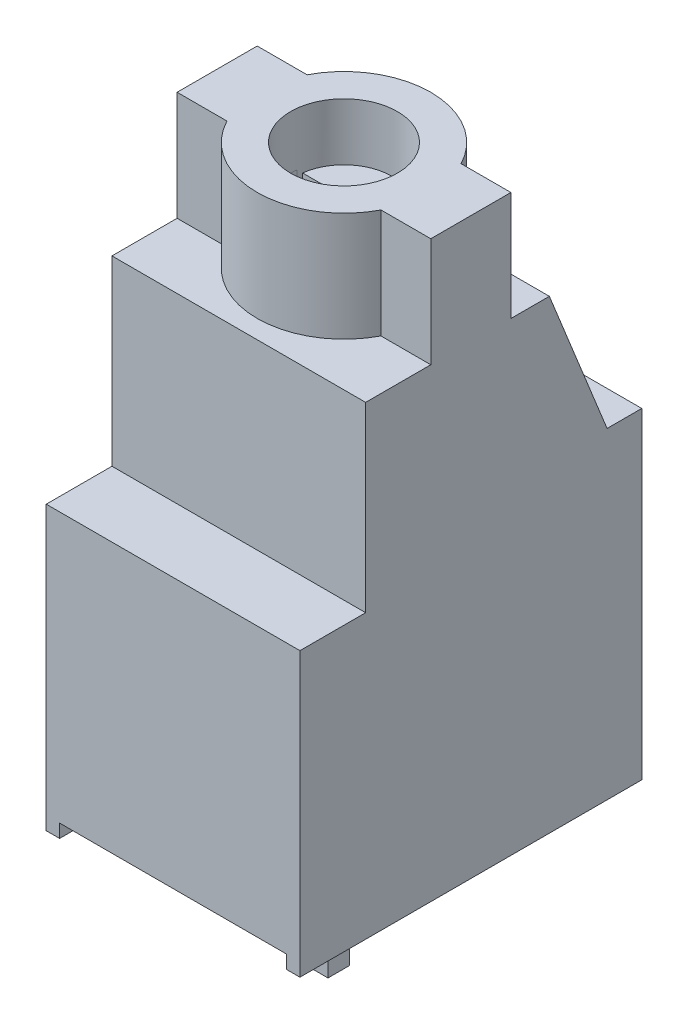
SolidWorks part; units mm, degrees
ref_plane "前视基准面" through (0, 0, 0) normal (0, 0, 1) x (1, 0, 0)
ref_plane "上视基准面" through (0, 0, 0) normal (0, 1, 0) x (1, 0, 0)
ref_plane "右视基准面" through (0, 0, 0) normal (1, 0, 0) x (0, 0, -1)
sketch "草图2" plane through (0, 0, 0) normal (1, 0, 0) x (0, 0, -1)
  line L0 (6.4, 0) -> (-6.4, 0)
  line L1 (-6.4, 0) -> (-6.4, 10.5915)
  line L2 (-6.4, 10.5915) -> (-3.9397, 10.5915)
  line L3 (-3.9397, 10.5915) -> (-3.9397, 17.413)
  line L4 (-3.9397, 17.413) -> (-1.5, 17.413)
  line L5 (-1.5, 17.413) -> (-1.5, 21.5)
  line L6 (-1.5, 21.5) -> (1.5, 21.5)
  line L7 (1.5, 21.5) -> (1.5, 17.413)
  line L8 (5.102, 12.0465) -> (2.94, 17.413)
  line L9 (5.102, 12.0465) -> (6.4, 12.0465)
  line L10 (6.4, 12.0465) -> (6.4, 0)
  line L11 (0, 82.2465) -> (0, -29.6489) construction
  line L12 (2.94, 17.413) -> (1.5, 17.413)
  dimension "D1" = 12.8
  dimension "D2" = 21.5
  dimension "D3" = 3
extrude "凸台-拉伸1" add sketch "草图2" along normal blind 4.75 and the other way blind 4.75
sketch "草图3" plane through (0, 21.5, 0) normal (0, 1, 0) x (1, 0, 0)
  circle A0 centre (0, 0) radius 3.25
  dimension "D1" = 6.5
extrude "凸台-拉伸2" add sketch "草图3" against normal up to next (21.5 mm away)
sketch "草图4" plane through (0, 21.5, 0) normal (0, 1, 0) x (1, 0, 0)
  circle A0 centre (0, 0) radius 2
  dimension "D1" = 4
extrude "切除-拉伸1" cut sketch "草图4" against normal blind 2
sketch "草图7" plane through (0, 19.5, 0) normal (0, 1, 0) x (1, 0, 0)
  circle A1 centre (0, 0) radius 2 construction
  circle A2 centre (0, 0) radius 2
  circle A3 centre (0, 0) radius 1.8
  dimension "D1" = 0.2
extrude "切除-拉伸5" cut sketch "草图7" against normal blind 0.5
sketch "草图5" plane through (0, 19.5, 0) normal (0, 1, 0) x (1, 0, 0)
  line L0 (2.9198, 0) -> (-3.0795, 0) construction
  line L1 (-2, 0.232) -> (2, 0.232)
  line L2 (-2, 0.232) -> (-2, -0.232)
  line L3 (-2, -0.232) -> (2, -0.232)
  line L4 (2, 0.232) -> (2, -0.232)
  line L5 (0, 1.1079) -> (0, -1.2643) construction
  circle A0 centre (0, 0) radius 2 construction
extrude "切除-拉伸2" cut sketch "草图5" against normal blind 0.5
sketch "草图8" plane through (0, 0, -6.4) normal (0, 0, -1) x (-1, 0, 0)
  line L0 (0, -8.4917) -> (0, 27.7719) construction
  line L2 (-1.9173, 7.8501) -> (1.9173, 7.8501)
  line L3 (-1.9173, 7.8501) -> (-1.9173, 4.0836)
  line L4 (-1.9173, 4.0836) -> (1.9173, 4.0836)
  line L5 (1.9173, 7.8501) -> (1.9173, 4.0836)
extrude "切除-拉伸6" cut sketch "草图8" against normal blind 2
chamfer "倒角1" distance 1 angle 60 4 edges at (0, 7.8501, -6.4) (-1.9173, 5.9668, -6.4) (1.9173, 5.9668, -6.4) (0, 4.0836, -6.4) first distance on face at (0, 5.9668, -6.4)
sketch "草图9" plane through (0, 0, 0) normal (0, -1, 0) x (1, 0, 0)
  line L0 (-4.75, 6.4) -> (4.75, 6.4) construction
  line L1 (-4.25, 6.4) -> (4.25, 6.4)
  line L2 (-4.25, 6.4) -> (-4.25, -6.4)
  line L3 (-4.25, -6.4) -> (4.25, -6.4)
  line L4 (4.25, 6.4) -> (4.25, -6.4)
  line L5 (-4.75, -6.4) -> (4.75, -6.4) construction
  line L6 (0, 11.6522) -> (0, -12.157) construction
  line L7 (-4.75, 6.4) -> (-4.75, -6.4) construction
  line L8 (4.75, 6.4) -> (4.75, -6.4) construction
  point P10 (-4.75, 0)
  dimension "D1" = 0.5
  dimension "D2" = 0.5
extrude "切除-拉伸7" cut sketch "草图9" against normal blind 0.5
sketch "草图10" plane through (0, 0.5, 0) normal (0, -1, 0) x (1, 0, 0)
  line L0 (0, 2.8369) -> (0, -1.126) construction
  line L1 (-0.6, 1.2) -> (0.6, 1.2)
  line L2 (-0.6, 1.2) -> (-0.6, 0.4)
  line L3 (-0.6, 0.4) -> (0.6, 0.4)
  line L4 (0.6, 1.2) -> (0.6, 0.4)
  line L5 (-1.1133, 0.8) -> (0.9224, 0.8) construction
  line L6 (4.25, 6.4) -> (-4.25, 6.4) construction
  dimension "D1" = 1.2
  dimension "D2" = 0.8
  dimension "D3" = 5.6
extrude "凸台-拉伸4" add sketch "草图10" along normal blind 5.2
